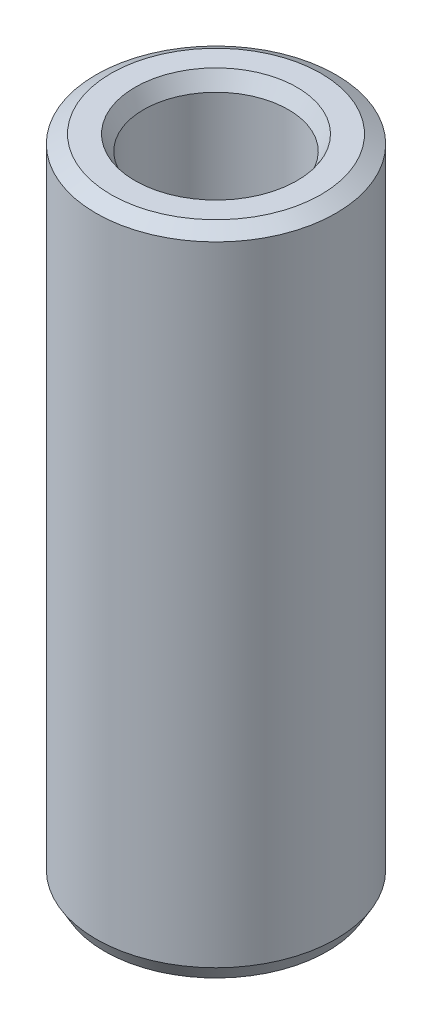
SolidWorks part; units mm, degrees
ref_plane "Front Plane" through (0, 0, 0) normal (0, 0, 1) x (1, 0, 0)
ref_plane "Top Plane" through (0, 0, 0) normal (0, 1, 0) x (1, 0, 0)
ref_plane "Right Plane" through (0, 0, 0) normal (1, 0, 0) x (0, 0, -1)
sketch "Sketch1" plane through (0, 0, 0) normal (0, 1, 0) x (1, 0, 0)
  circle A0 centre (0, 0) radius 20
  dimension "SLEEVE_OD" = 40
extrude "Boss-Extrude1" add sketch "Sketch1" along normal blind 108.7013
sketch "Sketch2" plane through (0, 0, 0) normal (0, 1, 0) x (1, 0, 0)
  circle A0 centre (0, 0) radius 12.0542
  dimension "BORE_D" = 24.1085
extrude "Cut-Extrude1" cut sketch "Sketch2" along normal through all
chamfer "Chamfer1" distance 1.4421 angle 60 4 edges at (0, 108.7013, 12.0542) (0, 0, 12.0542) (0, 0, 20) (0, 108.7013, 20) first distance on face at (0, 108.7013, 12.0542) first distance on face at (0, 0, 12.0542) first distance on face at (0, 108.7013, 20)
